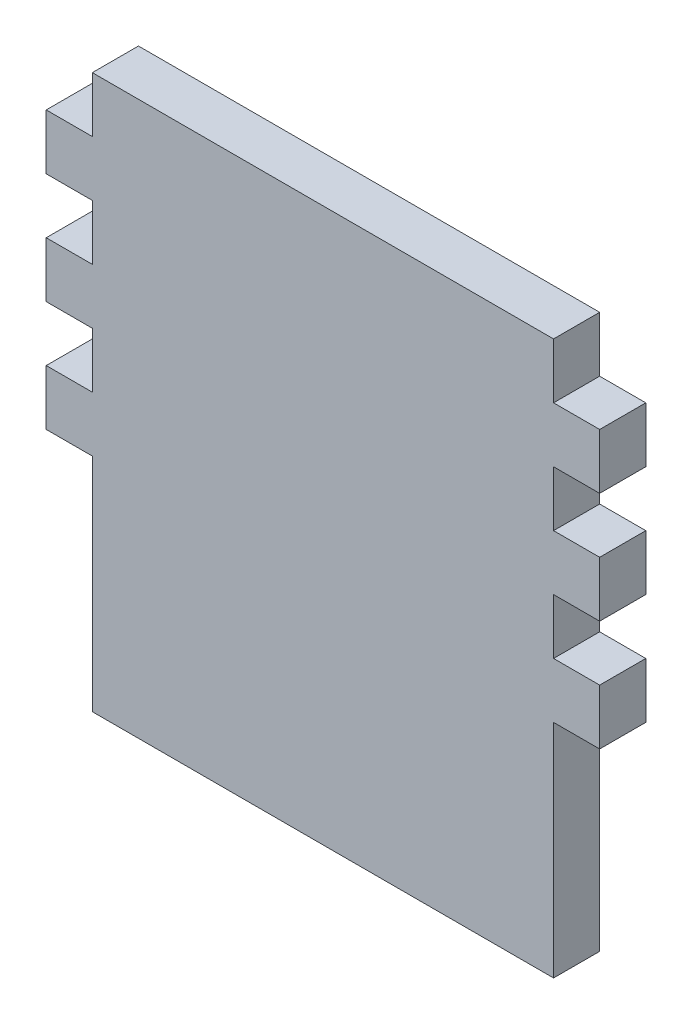
SolidWorks part; units mm, degrees
ref_plane "Front Plane" through (0, 0, 0) normal (0, 0, 1) x (1, 0, 0)
ref_plane "Top Plane" through (0, 0, 0) normal (0, 1, 0) x (1, 0, 0)
ref_plane "Right Plane" through (0, 0, 0) normal (1, 0, 0) x (0, 0, -1)
sketch "Sketch1" plane through (0, 0, 0) normal (0, 0, 1) x (1, 0, 0)
  line L1 (-37.8801, 17.0433) -> (38.3199, 17.0433)
  line L2 (-37.8801, 17.0433) -> (-37.8801, -59.1567)
  line L3 (-37.8801, -59.1567) -> (38.3199, -59.1567)
  line L4 (38.3199, 17.0433) -> (38.3199, -59.1567)
  dimension "D1" = 76.2
  dimension "D2" = 76.2
extrude "Boss-Extrude1" add sketch "Sketch1" along normal blind 6.35
sketch "Sketch2" plane through (0, 0, 6.35) normal (0, 0, 1) x (1, 0, 0)
  line L0 (-37.8801, 17.0433) -> (-31.5301, 17.0433)
  line L1 (38.3199, 17.0433) -> (-37.8801, 17.0433) construction
  line L2 (-31.5301, 17.0433) -> (-31.5301, 9.4233)
  line L3 (-31.5301, 9.4233) -> (-37.8801, 9.4233)
  line L4 (-37.8801, 17.0433) -> (-37.8801, -59.1567) construction
  line L5 (-37.8801, 9.4233) -> (-37.8801, 1.8033)
  line L6 (-37.8801, 1.8033) -> (-31.5301, 1.8033)
  line L7 (-31.5301, 1.8033) -> (-31.5301, -5.8167)
  line L8 (-31.5301, -5.8167) -> (-37.8801, -5.8167)
  line L9 (-37.8801, -5.8167) -> (-37.8801, -13.4367)
  line L10 (-37.8801, -13.4367) -> (-31.5301, -13.4367)
  line L11 (-31.5301, -13.4367) -> (-31.5301, -21.0567)
  line L12 (-31.5301, -21.0567) -> (-37.8801, -21.0567)
  line L13 (-37.8801, -21.0567) -> (-46.7258, -21.0567)
  line L14 (-37.8801, -21.0567) -> (-37.8801, -28.6767) [skipped]
  line L15 (-46.7258, -21.0567) -> (-46.7258, 17.0433)
  line L16 (-46.7258, 17.0433) -> (-37.8801, 17.0433)
  line L19 (47.1657, -21.0567) -> (47.1657, 17.0433)
  line L20 (38.3199, -21.0567) -> (47.1657, -21.0567)
  line L21 (31.9699, -21.0567) -> (38.3199, -21.0567)
  line L22 (31.9699, -13.4367) -> (31.9699, -21.0567)
  line L23 (38.3199, -13.4367) -> (31.9699, -13.4367)
  line L24 (38.3199, -5.8167) -> (38.3199, -13.4367)
  line L25 (31.9699, -5.8167) -> (38.3199, -5.8167)
  line L26 (31.9699, 1.8033) -> (31.9699, -5.8167)
  line L27 (38.3199, 1.8033) -> (31.9699, 1.8033)
  line L28 (38.3199, 9.4233) -> (38.3199, 1.8033)
  line L29 (31.9699, 9.4233) -> (38.3199, 9.4233)
  line L30 (31.9699, 17.0433) -> (31.9699, 9.4233)
  line L31 (38.3199, 17.0433) -> (31.9699, 17.0433)
  line L32 (47.1657, 17.0433) -> (38.3199, 17.0433)
  dimension "D1" = 7.62
  dimension "D2" = 7.62
  dimension "D3" = 6.35
  dimension "D4" = 6.35
  dimension "D6" = 38.1
  dimension "D5" = 3
extrude "Cut-Extrude1" cut sketch "Sketch2" against normal blind 6.35
sketch "Sketch3" plane through (0, 0, 6.35) normal (0, 0, 1) x (1, 0, 0)
  line L1 (-31.5301, -21.0567) -> (-37.8801, -21.0567)
  line L2 (-31.5301, -21.0567) -> (-31.5301, -59.1567)
  line L3 (-31.5301, -59.1567) -> (-37.8801, -59.1567)
  line L4 (-37.8801, -21.0567) -> (-37.8801, -59.1567)
  line L5 (31.9699, -21.0567) -> (38.3199, -21.0567)
  line L6 (31.9699, -21.0567) -> (31.9699, -59.1567)
  line L7 (31.9699, -59.1567) -> (38.3199, -59.1567)
  line L8 (38.3199, -21.0567) -> (38.3199, -59.1567)
extrude "Cut-Extrude2" cut sketch "Sketch3" against normal blind 6.35
sketch "Sketch4" plane through (0, 0, 6.35) normal (0, 0, 1) x (1, 0, 0)
  line L0 (-31.5301, -13.4367) -> (-31.5301, -21.0567)
  line L1 (-31.5301, -59.1567) -> (-31.5301, -13.4367) construction
  line L2 (-31.5301, -21.0567) -> (-37.8801, -21.0567)
  line L3 (-37.8801, -21.0567) -> (-37.8801, -28.6767)
  line L4 (-37.8801, -28.6767) -> (-31.5301, -28.6767)
  line L5 (-31.5301, -21.0567) -> (-31.5301, -28.6767)
  line L6 (0.2199, 17.0433) -> (0.2199, -59.1567)
  line L7 (31.9699, 17.0433) -> (-31.5301, 17.0433) construction
  line L8 (-31.5301, -59.1567) -> (31.9699, -59.1567) construction
  line L9 (31.9699, -21.0567) -> (38.3199, -21.0567)
  line L10 (38.3199, -21.0567) -> (38.3199, -28.6767)
  line L11 (38.3199, -28.6767) -> (31.9699, -28.6767)
  line L12 (31.9699, -21.0567) -> (31.9699, -28.6767)
  line M6 (-31.5301, -13.4367) -> (-31.5301, -59.1567)
  line M8 (31.9699, -59.1567) -> (31.9699, -13.4367)
  dimension "D1" = 7.62
  dimension "D2" = 7.62
  dimension "D3" = 6.35
  dimension "D4" = 6.35
extrude "Boss-Extrude3" add sketch "Sketch4" against normal blind 6.35 contours L3 L4 L2 M6 | L11 L10 L9 M8 region at (-34.7051, -24.8667, 6.35) region at (35.1449, -24.8667, 6.35)
